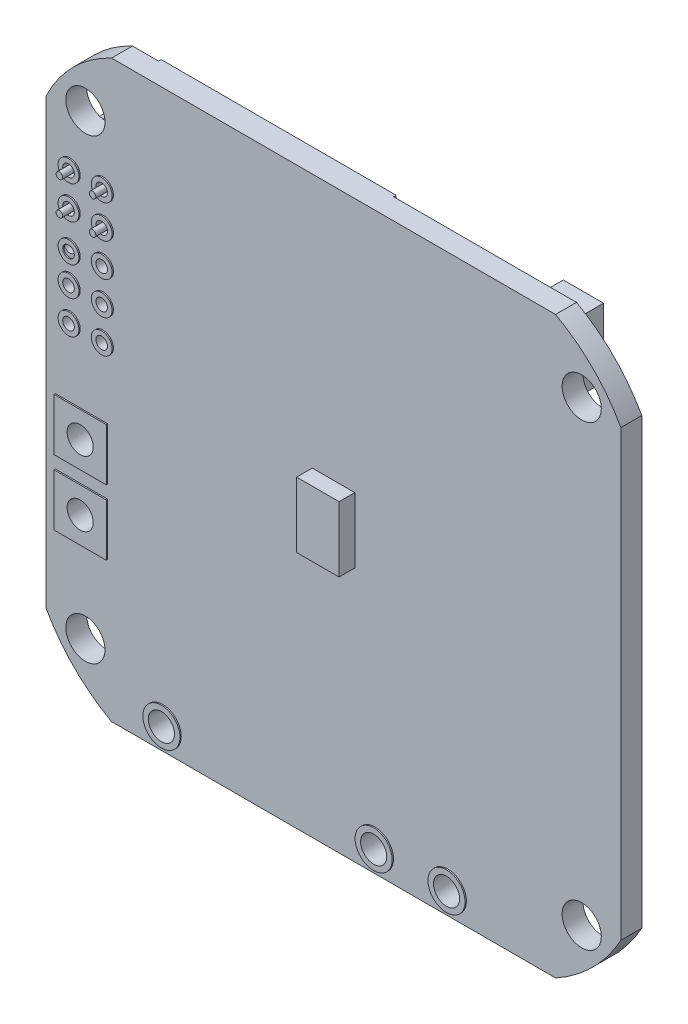
SolidWorks part; units mm, degrees
material "6061-T6 (SS)"
ref_plane "Alzado" through (0, 0, 0) normal (0, 0, 1) x (1, 0, 0)
ref_plane "Planta" through (0, 0, 0) normal (0, 1, 0) x (1, 0, 0)
ref_plane "Vista lateral" through (0, 0, 0) normal (1, 0, 0) x (0, 0, -1)
sketch "Croquis1" plane through (0, 0, 0) normal (0, 0, 1) x (1, 0, 0)
  line L0 (-22, 17) -> (-22, -17)
  line L1 (0, 0) -> (0, -6.2515) construction
  line L2 (22, 17) -> (22, -17)
  line L3 (-17, -22) -> (17, -22)
  line L4 (0, 0) -> (8.2976, 0) construction
  line L5 (-17, 22) -> (17, 22)
  arc A0 (-17, 22) -> (-22, 17) centre (-12.5089, 12.5089) ccw
  arc A2 (17, -22) -> (22, -17) centre (10.8379, -10.8379) ccw
  arc A3 (-22, -17) -> (-17, -22) centre (-10.8379, -10.8379) ccw
  arc A7 (22, 17) -> (17, 22) centre (10.8379, 10.8379) ccw
  point P0 (0, 0)
  point P4 (-22, 0)
  point P13 (0, -22)
  dimension "D3" = 21
  dimension "D4" = 34
  dimension "D1" = 34
  dimension "D2" = 22
  dimension "D5" = 22
extrude "Saliente-Extruir1" add sketch "Croquis1" along normal mid plane 1.6
sketch "Croquis2" plane through (0, 0, 0.8) normal (0, 0, 1) x (1, 0, 0)
  line L1 (19, -17.5) -> (-19, -17.5) construction
  line L2 (19, -17.5) -> (19, 17.5) construction
  line L3 (19, 17.5) -> (-19, 17.5) construction
  line L4 (-19, -17.5) -> (-19, 17.5) construction
  line L5 (19, -17.5) -> (-19, 17.5) construction
  line L6 (19, 17.5) -> (-19, -17.5) construction
  circle A0 centre (-19, 17.5) radius 1.5
  circle A1 centre (19, 17.5) radius 1.5
  circle A2 centre (19, -17.5) radius 1.5
  circle A3 centre (-19, -17.5) radius 1.5
  point P0 (0, 0)
  dimension "D1" = 3
  dimension "D2" = 38
  dimension "D3" = 35
extrude "Cortar-Extruir1" cut sketch "Croquis2" against normal through all
sketch "Croquis3" plane through (0, 0, 0.8) normal (0, 0, 1) x (1, 0, 0)
  line L1 (-1.625, 2.5) -> (1.625, 2.5)
  line L2 (-1.625, 2.5) -> (-1.625, -2.5)
  line L3 (-1.625, -2.5) -> (1.625, -2.5)
  line L4 (1.625, 2.5) -> (1.625, -2.5)
  line L5 (-1.625, 2.5) -> (1.625, -2.5) construction
  line L6 (-1.625, -2.5) -> (1.625, 2.5) construction
  point P0 (0, 0)
  dimension "D1" = 5
  dimension "D2" = 3.25
extrude "Saliente-Extruir2" add sketch "Croquis3" along normal blind 1.2
sketch "Croquis4" plane through (0, 0, -0.8) normal (0, 0, -1) x (-1, 0, 0)
  line L0 (22, 17) -> (22, -17) construction
  line L1 (-17, 22) -> (17, 22) construction
  circle A0 centre (17.653, 13) radius 0.445
  circle A1 centre (20.193, 13) radius 0.445
  circle A2 centre (20.193, 10.46) radius 0.445
  circle A3 centre (20.193, 7.92) radius 0.445
  circle A4 centre (20.193, 5.38) radius 0.445
  circle A5 centre (20.193, 2.84) radius 0.445
  circle A6 centre (17.653, 10.46) radius 0.445
  circle A7 centre (17.653, 7.92) radius 0.445
  circle A8 centre (17.653, 5.38) radius 0.445
  circle A9 centre (17.653, 2.84) radius 0.445
  dimension "D1" = 0.89
  dimension "D3" = 1.807
  dimension "D4" = 9
  dimension "D5" = 2.54
  dimension "D2" = 5
extrude "Cortar-Extruir2" cut sketch "Croquis4" against normal through all
sketch "Croquis5" plane through (0, 0, 0) normal (0, 0, 1) x (1, 0, 0)
  line L0 (-17, -22) -> (17, -22) construction
  line L1 (-17.3, -2.4) -> (-21.3, -2.4)
  line L2 (-17.3, -2.4) -> (-17.3, -6.4)
  line L3 (-17.3, -6.4) -> (-21.3, -6.4)
  line L4 (-21.3, -2.4) -> (-21.3, -6.4)
  line L5 (-17.3, -2.4) -> (-21.3, -6.4) construction
  line L6 (-17.3, -6.4) -> (-21.3, -2.4) construction
  line L7 (-17.3, -7.4) -> (-21.3, -7.4)
  line L8 (-17.3, -7.4) -> (-17.3, -11.4)
  line L9 (-17.3, -11.4) -> (-21.3, -11.4)
  line L10 (-21.3, -7.4) -> (-21.3, -11.4)
  line L11 (-17.3, -7.4) -> (-21.3, -11.4) construction
  line L12 (-17.3, -11.4) -> (-21.3, -7.4) construction
  line L13 (-22, 17) -> (-22, -17) construction
  circle A0 centre (-17.653, 2.84) radius 0.7974
  circle A1 centre (-20.193, 2.84) radius 0.7974
  circle A2 centre (-20.193, 5.38) radius 0.7974
  circle A3 centre (-17.653, 5.38) radius 0.7974
  circle A4 centre (-17.653, 7.92) radius 0.7974
  circle A5 centre (-17.653, 10.46) radius 0.7974
  circle A6 centre (-20.193, 7.62) radius 0.7974
  circle A7 centre (-20.193, 10.46) radius 0.7974
  circle A8 centre (-17.653, 13) radius 0.7974
  circle A9 centre (-20.193, 13) radius 0.7974
  circle A10 centre (-17.653, 13) radius 0.445
  circle A11 centre (-20.193, 13) radius 0.445
  circle A12 centre (-20.193, 10.46) radius 0.445
  circle A13 centre (-17.653, 10.46) radius 0.445
  circle A14 centre (-17.653, 7.92) radius 0.445
  circle A15 centre (-20.193, 7.62) radius 0.445
  circle A16 centre (-20.193, 5.38) radius 0.445
  circle A17 centre (-17.653, 5.38) radius 0.445
  circle A18 centre (-17.653, 2.84) radius 0.445
  circle A19 centre (-20.193, 2.84) radius 0.445
  point P0 (-19.3, -4.4)
  point P5 (-19.3, -9.4)
  dimension "D1" = 4
  dimension "D2" = 4
  dimension "D3" = 5
  dimension "D4" = 4
  dimension "D5" = 4
  dimension "D6" = 12.6
  dimension "D7" = 2.7
extrude "Saliente-Extruir3" add sketch "Croquis5" along normal mid plane 1.8
sketch "Croquis6" plane through (0, 0, -0.9) normal (0, 0, -1) x (-1, 0, 0)
  line L0 (21.3, -2.4) -> (21.3, -6.4) construction
  line L1 (21.3, -7.4) -> (21.3, -11.4) construction
  circle A0 centre (19.3, -4.4) radius 1
  circle A1 centre (19.3, -9.4) radius 1
  point P6 (21.3, -4.4)
  point P9 (21.3, -9.4)
  dimension "D1" = 2
extrude "Cortar-Extruir3" cut sketch "Croquis6" against normal through all both and the other way through all
sketch "Croquis7" plane through (0, 0, -0.8) normal (0, 0, -1) x (-1, 0, 0)
  line L0 (17, -22) -> (-17, -22) construction
  line L1 (22, 17) -> (22, -17) construction
  circle A0 centre (-8.75, -20.32) radius 1
  circle A1 centre (-3.17, -20.32) radius 1
  circle A2 centre (13.08, -20.32) radius 1
  dimension "D1" = 2
  dimension "D2" = 1.68
  dimension "D3" = 5.58
  dimension "D4" = 16.25
  dimension "D5" = 8.92
extrude "Cortar-Extruir4" cut sketch "Croquis7" against normal blind 10
sketch "Croquis8" plane through (0, 0, -0.8) normal (0, 0, -1) x (-1, 0, 0)
  line L0 (-22, -17) -> (-22, 17) construction
  line L1 (-20.5, 13.45) -> (-17.5, 13.45)
  line L2 (-20.5, 13.45) -> (-20.5, 10.95)
  line L3 (-20.5, 10.95) -> (-17.5, 10.95)
  line L4 (-17.5, 13.45) -> (-17.5, 10.95)
  line L5 (-20.5, 10.275) -> (-17.5, 10.275)
  line L6 (-20.5, 10.275) -> (-20.5, 7.775)
  line L7 (-20.5, 7.775) -> (-17.5, 7.775)
  line L8 (-17.5, 10.275) -> (-17.5, 7.775)
  line L10 (-17, 22) -> (17, 22) construction
  point P8 (-19, 7.775)
  point P11 (-20.5, 12.2)
  point P12 (-20.5, 9.025)
  point P15 (-17.5, 12.2)
  dimension "D1" = 3
  dimension "D2" = 3
  dimension "D3" = 2.5
  dimension "D4" = 3.175
  dimension "D5" = 9.8
extrude "Saliente-Extruir4" add sketch "Croquis8" along normal blind 1.2
sketch "Croquis9" plane through (0, 0, -2) normal (0, 0, -1) x (-1, 0, 0)
  line L0 (-17.5, 13.45) -> (-20.5, 13.45) construction
  line L1 (-17.5, 7.775) -> (-17.5, 10.275) construction
  line L2 (-17.5, 10.95) -> (-17.5, 13.45) construction
  circle A0 centre (-19, 12.2) radius 0.75
  circle A1 centre (-19, 9.025) radius 0.75
  point P7 (-19, 13.45)
  point P10 (-17.5, 9.025)
  point P14 (-17.5, 12.2)
  dimension "D1" = 1.5
extrude "Saliente-Extruir5" add sketch "Croquis9" along normal blind 0.8
sketch "Croquis10" plane through (0, 0, -0.8) normal (0, 0, -1) x (-1, 0, 0)
  line L0 (-22, -17) -> (-22, 17) construction
  line L1 (-16, -14.25) -> (-11, -14.25)
  line L2 (-16, -14.25) -> (-16, -19.25)
  line L3 (-16, -19.25) -> (-11, -19.25)
  line L4 (-11, -14.25) -> (-11, -19.25)
  line L5 (17, -22) -> (-17, -22) construction
  line L6 (11.25, -12.2) -> (16.25, -12.2)
  line L7 (11.25, -12.2) -> (11.25, -17.2)
  line L8 (11.25, -17.2) -> (16.25, -17.2)
  line L9 (16.25, -12.2) -> (16.25, -17.2)
  line L10 (5.8877, -14.25) -> (10.8877, -14.25)
  line L11 (5.8877, -14.25) -> (5.8877, -19.25)
  line L12 (5.8877, -19.25) -> (10.8877, -19.25)
  line L13 (10.8877, -14.25) -> (10.8877, -19.25)
  line L14 (0.4343, -14.25) -> (5.4343, -14.25)
  line L15 (0.4343, -14.25) -> (0.4343, -19.25)
  line L16 (0.4343, -19.25) -> (5.4343, -19.25)
  line L17 (5.4343, -14.25) -> (5.4343, -19.25)
  line L18 (22, 17) -> (22, -17) construction
  line L19 (-4.9483, -12.2) -> (0.0517, -12.2)
  line L20 (-4.9483, -12.2) -> (-4.9483, -17.2)
  line L21 (-4.9483, -17.2) -> (0.0517, -17.2)
  line L22 (0.0517, -12.2) -> (0.0517, -17.2)
  line L23 (-10.5433, -12.2) -> (-5.5433, -12.2)
  line L24 (-10.5433, -12.2) -> (-10.5433, -17.2)
  line L25 (-10.5433, -17.2) -> (-5.5433, -17.2)
  line L26 (-5.5433, -12.2) -> (-5.5433, -17.2)
  dimension "D1" = 5
  dimension "D2" = 5
  dimension "D3" = 6
  dimension "D4" = 2.75
  dimension "D5" = 5
  dimension "D6" = 5
  dimension "D7" = 5
  dimension "D8" = 5
  dimension "D9" = 5
  dimension "D10" = 5
  dimension "D11" = 5.75
  dimension "D12" = 4.8
  dimension "D13" = 5
  dimension "D14" = 5
  dimension "D15" = 5
  dimension "D16" = 5
extrude "Saliente-Extruir6" add sketch "Croquis10" along normal blind 0.9
sketch "Croquis11" plane through (0, 0, -0.8) normal (0, 0, -1) x (-1, 0, 0)
  line L0 (-13.6529, -19.5225) -> (-10.4593, -19.5225)
  line L1 (-10.4593, -19.5225) -> (-9.8124, -18.8756)
  line L2 (-9.8124, -18.8756) -> (-7.529, -18.8756)
  line L3 (-7.529, -18.8756) -> (-7.1476, -19.257)
  line L4 (-7.1476, -19.257) -> (-7.1476, -21.3437)
  line L5 (-7.1476, -21.3437) -> (-7.529, -21.7251)
  line L6 (-7.529, -21.7251) -> (-13.8301, -21.7251)
  line L7 (-13.8301, -21.7251) -> (-14.1414, -21.4138)
  line L8 (-14.1414, -21.4138) -> (-14.1414, -20.011)
  line L9 (-14.1414, -20.011) -> (-13.6529, -19.5225)
  line L10 (8.1723, -19.5225) -> (11.1983, -19.5225)
  line L11 (11.1983, -19.5225) -> (12.0225, -18.6983)
  line L12 (12.0225, -18.6983) -> (14.2962, -18.6983)
  line L13 (14.2962, -18.6983) -> (14.7785, -19.1806)
  line L14 (14.7785, -19.1806) -> (14.7785, -21.2429)
  line L15 (14.7785, -21.2429) -> (14.2962, -21.7251)
  line L16 (14.2962, -21.7251) -> (7.9951, -21.7251)
  line L17 (7.9951, -21.7251) -> (7.6839, -21.4138)
  line L18 (7.6839, -21.4138) -> (7.6839, -20.011)
  line L19 (7.6839, -20.011) -> (8.1723, -19.5225)
  line L20 (2.2631, -20.011) -> (1.7746, -19.5225)
  line L21 (2.2631, -21.4138) -> (2.2631, -20.011)
  line L22 (1.9518, -21.7251) -> (2.2631, -21.4138)
  line L23 (-4.3493, -21.7251) -> (1.9518, -21.7251)
  line L24 (-4.7307, -21.3437) -> (-4.3493, -21.7251)
  line L25 (-4.7307, -19.257) -> (-4.7307, -21.3437)
  line L26 (-4.3493, -18.8756) -> (-4.7307, -19.257)
  line L27 (-2.0659, -18.8756) -> (-4.3493, -18.8756)
  line L28 (-1.4189, -19.5225) -> (-2.0659, -18.8756)
  line L29 (1.7746, -19.5225) -> (-1.4189, -19.5225)
  line L30 (-5.9391, -18.0693) -> (-5.9391, -23.1735) construction
  circle A0 centre (-8.75, -20.32) radius 1
  circle A1 centre (-3.17, -20.32) radius 1
  circle A2 centre (13.08, -20.32) radius 1
extrude "Saliente-Extruir7" add sketch "Croquis11" along normal blind 0.1
sketch "Croquis12" plane through (0, 0, -0.8) normal (0, 0, -1) x (-1, 0, 0)
  line L0 (-19.5752, -2.7898) -> (-13.4845, -8.8805)
  line L1 (-19.5752, -2.7898) -> (-13.4845, 3.301)
  line L2 (-13.4845, -8.8805) -> (-7.3937, -2.7898)
  line L3 (-13.4845, 3.301) -> (-7.3937, -2.7898)
  line L4 (17, -22) -> (-17, -22) construction
  dimension "D1" = 45
extrude "Saliente-Extruir8" add sketch "Croquis12" along normal blind 0.75
sketch "Croquis13" plane through (0, 0, -0.8) normal (0, 0, -1) x (-1, 0, 0)
  line L1 (-16.4217, 20.3319) -> (-13.3413, 20.3319)
  line L2 (-16.4217, 20.3319) -> (-16.4217, 15.0982)
  line L3 (-16.4217, 15.0982) -> (-13.3413, 15.0982)
  line L4 (-13.3413, 20.3319) -> (-13.3413, 15.0982)
extrude "Saliente-Extruir9" add sketch "Croquis13" along normal blind 2.65
sketch "Croquis14" plane through (0, 0, -0.8) normal (0, 0, -1) x (-1, 0, 0)
  line L1 (-12.0511, 17.4084) -> (-8.2311, 17.4084)
  line L2 (-12.0511, 17.4084) -> (-12.0511, 13.5884)
  line L3 (-12.0511, 13.5884) -> (-8.2311, 13.5884)
  line L4 (-8.2311, 17.4084) -> (-8.2311, 13.5884)
  dimension "D1" = 3.82
extrude "Saliente-Extruir10" add sketch "Croquis14" along normal blind 3
sketch "Croquis30" plane through (0, 0, 0.8) normal (0, 0, 1) x (1, 0, 0)
  circle A0 centre (-13.08, -20.32) radius 1.4199
  circle A1 centre (8.75, -20.32) radius 1.4199
  circle A2 centre (3.17, -20.32) radius 1.4199
  circle A3 centre (-13.08, -20.32) radius 1
  circle A4 centre (3.17, -20.32) radius 1
  circle A5 centre (8.75, -20.32) radius 1
extrude "Saliente-Extruir17" add sketch "Croquis30" along normal blind 0.1
sketch "Croquis29" plane through (0, 0, -0.8) normal (0, 0, -1) x (-1, 0, 0)
  line L0 (-17, 22) -> (17, 22) construction
  line L1 (10.5, 1.5) -> (14, 1.5)
  line L2 (10.5, 1.5) -> (10.5, 0)
  line L3 (10.5, 0) -> (14, 0)
  line L4 (14, 1.5) -> (14, 0)
  line L5 (10.5, -0.65) -> (14, -0.65)
  line L6 (10.5, -0.65) -> (10.5, -2.15)
  line L7 (10.5, -2.15) -> (14, -2.15)
  line L8 (14, -0.65) -> (14, -2.15)
  line L9 (2.75, 1.5) -> (6.25, 1.5)
  line L10 (2.75, 1.5) -> (2.75, 0)
  line L11 (2.75, 0) -> (6.25, 0)
  line L12 (6.25, 1.5) -> (6.25, 0)
  line L13 (22, 17) -> (22, -17) construction
  dimension "D1" = 3.5
  dimension "D2" = 1.5
  dimension "D3" = 0.65
  dimension "D4" = 3.5
  dimension "D5" = 20.5
  dimension "D6" = 11.5
  dimension "D7" = 7.75
extrude "Saliente-Extruir16" add sketch "Croquis29" along normal blind 0.5
chamfer "Chaflán1" distance 1 angle 45 4 edges at (12.0511, 17.4084, -2.3) (8.2311, 17.4084, -2.3) (12.0511, 13.5884, -2.3) (8.2311, 13.5884, -2.3)
sketch "Croquis31" plane through (0, 0, -0.8) normal (0, 0, -1) x (-1, 0, 0)
  line L0 (-17, 22) -> (17, 22) construction
  line L1 (-3, 22) -> (15, 22)
  line L2 (-3, 22) -> (-3, 2.65)
  line L3 (-3, 2.65) -> (15, 2.65)
  line L4 (15, 22) -> (15, 2.65)
  line L5 (22, 17) -> (22, -17) construction
  dimension "D1" = 19.35
  dimension "D2" = 18
  dimension "D3" = 7
sketch "Croquis32" plane through (0, 0, -0.9) normal (0, 0, -1) x (-1, 0, 0)
  circle A0 centre (17.653, 13) radius 0.65
  circle A1 centre (20.193, 13) radius 0.65
  circle A2 centre (20.193, 10.46) radius 0.65
  circle A3 centre (17.653, 10.46) radius 0.65
  dimension "D1" = 1.3
extrude "Saliente-Extruir18" add sketch "Croquis32" along normal blind 1.6
sketch "Croquis33" plane through (0, 0, -0.9) normal (0, 0, 1) x (1, 0, 0)
  circle A0 centre (-20.193, 13) radius 0.25
  circle A1 centre (-17.653, 13) radius 0.25
  circle A2 centre (-17.653, 10.46) radius 0.25
  circle A3 centre (-20.193, 10.46) radius 0.25
  dimension "D1" = 0.5
extrude "Saliente-Extruir19" add sketch "Croquis33" along normal blind 2.5
sketch "Croquis34" plane through (0, 0, -2.5) normal (0, 0, -1) x (-1, 0, 0)
  line L0 (16.388, 14.1102) -> (16.388, 11.9202)
  line L1 (16.388, 11.9202) -> (16.8728, 11.735)
  line L2 (16.8728, 11.735) -> (18.4226, 11.735)
  line L3 (18.4226, 11.735) -> (18.918, 11.8898)
  line L4 (18.918, 11.8898) -> (18.918, 14.1102)
  line L5 (18.918, 14.1102) -> (18.4332, 14.265)
  line L6 (18.4332, 14.265) -> (16.8728, 14.265)
  line L7 (16.8728, 14.265) -> (16.388, 14.1102)
  line L8 (17.653, 13) -> (17.653, 14.4547) construction
  line L9 (17.653, 13) -> (15.9852, 13) construction
  line L10 (18.9656, 14.1102) -> (18.9656, 11.9202)
  line L11 (18.9656, 11.9202) -> (19.4505, 11.735)
  line L12 (19.4505, 11.735) -> (21.0002, 11.735)
  line L13 (21.0002, 11.735) -> (21.4956, 11.8898)
  line L14 (21.4956, 11.8898) -> (21.4956, 14.1102)
  line L15 (21.4956, 14.1102) -> (21.0108, 14.265)
  line L16 (21.0108, 14.265) -> (19.4505, 14.265)
  line L17 (19.4505, 14.265) -> (18.9656, 14.1102)
  line L18 (20.2306, 13) -> (20.2306, 14.4547) construction
  line L19 (20.2306, 13) -> (18.5628, 13) construction
  line L20 (18.9656, 11.529) -> (18.9656, 9.339)
  line L21 (18.9656, 9.339) -> (19.4505, 9.1538)
  line L22 (19.4505, 9.1538) -> (21.0002, 9.1538)
  line L23 (21.0002, 9.1538) -> (21.4956, 9.3086)
  line L24 (21.4956, 9.3086) -> (21.4956, 11.529)
  line L25 (21.4956, 11.529) -> (21.0108, 11.6838)
  line L26 (21.0108, 11.6838) -> (19.4505, 11.6838)
  line L27 (19.4505, 11.6838) -> (18.9656, 11.529)
  line L28 (20.2306, 10.4188) -> (20.2306, 11.8735) construction
  line L29 (20.2306, 10.4188) -> (18.5628, 10.4188) construction
  line L30 (16.388, 11.529) -> (16.388, 9.339)
  line L31 (16.388, 9.339) -> (16.8728, 9.1538)
  line L32 (16.8728, 9.1538) -> (18.4226, 9.1538)
  line L33 (18.4226, 9.1538) -> (18.918, 9.3086)
  line L34 (18.918, 9.3086) -> (18.918, 11.529)
  line L35 (18.918, 11.529) -> (18.4332, 11.6838)
  line L36 (18.4332, 11.6838) -> (16.8728, 11.6838)
  line L37 (16.8728, 11.6838) -> (16.388, 11.529)
  line L38 (17.653, 10.4188) -> (17.653, 11.8735) construction
  line L39 (17.653, 10.4188) -> (15.9852, 10.4188) construction
  circle A0 centre (17.653, 13) radius 0.65
  circle A1 centre (20.2306, 13) radius 0.64
  circle A2 centre (20.2306, 10.4188) radius 0.6641
  circle A3 centre (17.653, 10.4188) radius 0.64
  point P2 (17.653, 14.265)
  point P9 (18.918, 13)
  dimension "D1" = 2.53
  dimension "D2" = 2.53
  dimension "D3" = 2
  dimension "D4" = 2
extrude "Saliente-Extruir20" add sketch "Croquis34" along normal blind 3
extrude "Boss-Extrude1" add sketch "Croquis31" along normal blind 0.2
